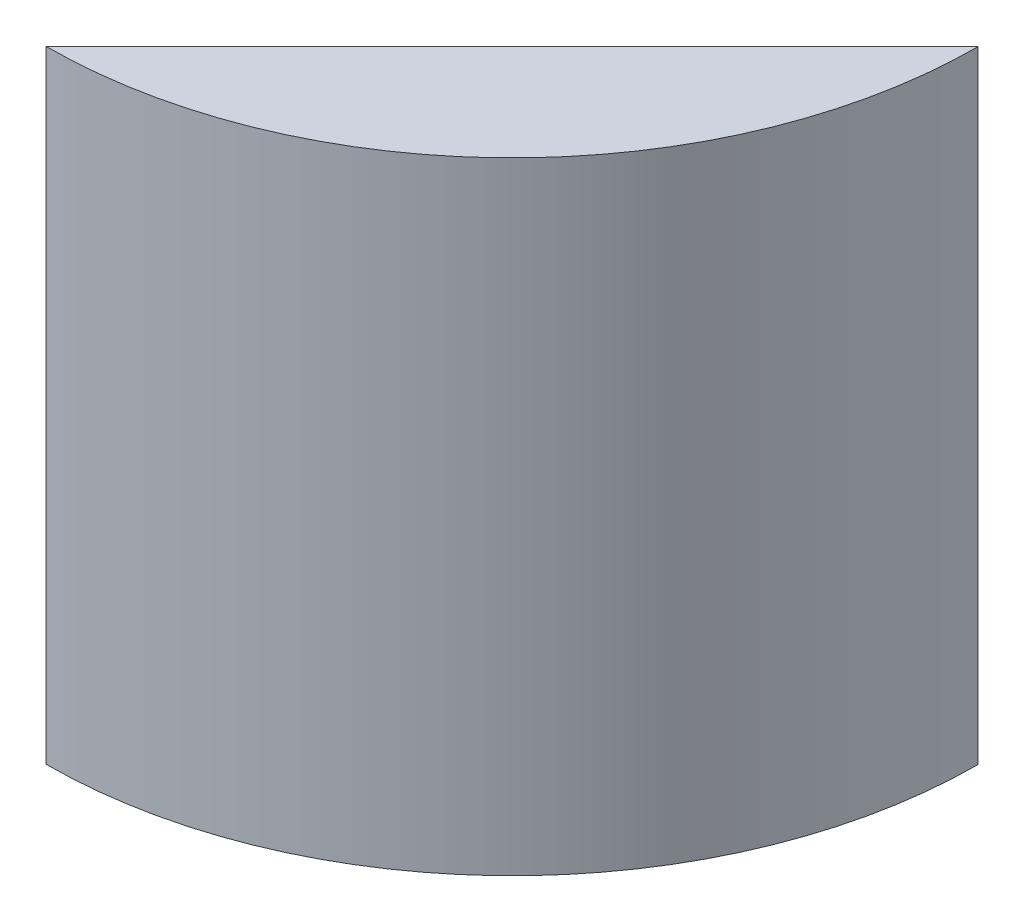
SolidWorks part; units mm, degrees
ref_plane "Front Plane" through (0, 0, 0) normal (0, 0, 1) x (1, 0, 0)
ref_plane "Top Plane" through (0, 0, 0) normal (0, 1, 0) x (1, 0, 0)
ref_plane "Right Plane" through (0, 0, 0) normal (1, 0, 0) x (0, 0, -1)
sketch "Sketch1" plane through (0, 0, 0) normal (0, 1, 0) x (1, 0, 0)
  circle A0 centre (0, 0) radius 85.725
  dimension "D1" = 171.45
extrude "Boss-Extrude1" add sketch "Sketch1" along normal blind 114.3
sketch "Sketch2" plane through (0, 114.3, 0) normal (0, 1, 0) x (1, 0, 0)
  line L0 (85.7249, -0.1067) -> (0, -85.725)
  line L1 (0, -85.725) -> (-45.6275, -96.7194)
  line L6 (-45.6275, -96.7194) -> (-137.4289, 46.1739)
  line L7 (-137.4289, 46.1739) -> (19.1253, 101.9105)
  line L8 (19.1253, 101.9105) -> (109.8339, 30.6005)
  line L9 (109.8339, 30.6005) -> (85.7249, -0.1067)
  circle A0 centre (0, 0) radius 85.725 construction
extrude "Cut-Extrude1" cut sketch "Sketch2" against normal blind 152.4
sketch "Sketch4" plane through (42.8625, 0, 42.9158) normal (-0.7067, 0, -0.7075) x (-0.7075, 0, 0.7067)
  line L1 (60.579, 0) -> (-60.579, 0) construction
  circle A0 centre (40.6185, 93.472) radius 2.7781
  circle A1 centre (-4.8475, 93.472) radius 2.7781
  circle A2 centre (-4.8475, 25.4) radius 2.7781
  circle A3 centre (40.6185, 25.4) radius 2.7781
  dimension "D1" = 25.4
  dimension "D3" = 45.466
  dimension "D2" = 68.072
  dimension "D4" = 68.072
  dimension "D5" = 45.466
extrude "Cut-Extrude2" cut sketch "Sketch4" against normal blind 12.7
sketch "Sketch5" plane through (0, 0, 0) normal (0, -1, 0) x (-1, 0, 0)
  line L2 (-25.1459, -25.1772) -> (-60.579, -60.6544) construction
  line L5 (0, -85.725) -> (-85.7249, -0.1067) construction
  circle A0 centre (-51.8371, -51.9017) radius 6.985
  arc A1 (-85.7249, -0.1067) -> (0, -85.725) centre (0, 0) ccw construction
  point P2 (0, 0)
  point P3 (0, 0)
  point P7 (-42.8625, -42.9158)
  point P10 (0, 0)
  point P11 (0, 0)
  point P12 (-35.6224, -67.1079)
  point P15 (0, 0)
  dimension "D1" = 13.97
  dimension "D2" = 12.7
extrude "Cut-Extrude3" cut sketch "Sketch5" against normal blind 6.35
